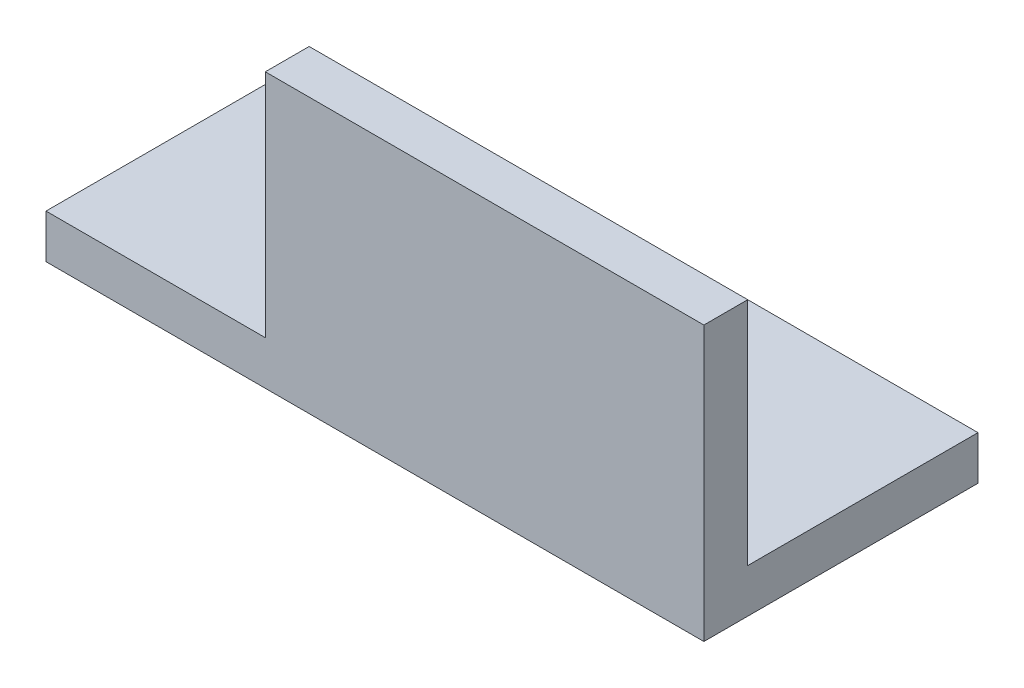
SolidWorks part; units mm, degrees
ref_plane "Спереди" through (0, 0, 0) normal (0, 0, 1) x (1, 0, 0)
ref_plane "Сверху" through (0, 0, 0) normal (0, 1, 0) x (1, 0, 0)
ref_plane "Справа" through (0, 0, 0) normal (1, 0, 0) x (0, 0, -1)
sketch "Эскиз1" plane through (0, 0, 0) normal (1, 0, 0) x (0, 0, -1)
  line L0 (0, 0) -> (25, 0)
  line L1 (0, 0) -> (0, 25)
extrude "Вытянуть-Тонкостенный1" add sketch "Эскиз1" along normal blind 60 thin thin type one direction wall 4
sketch "Эскиз2" plane through (0, 0, 0) normal (0, 0, 1) x (1, 0, 0)
  line L1 (0, 25) -> (20, 25)
  line L2 (0, 25) -> (0, 4)
  line L3 (0, 4) -> (20, 4)
  line L4 (20, 25) -> (20, 4)
extrude "Вырез-Вытянуть1" cut sketch "Эскиз2" against normal through all
